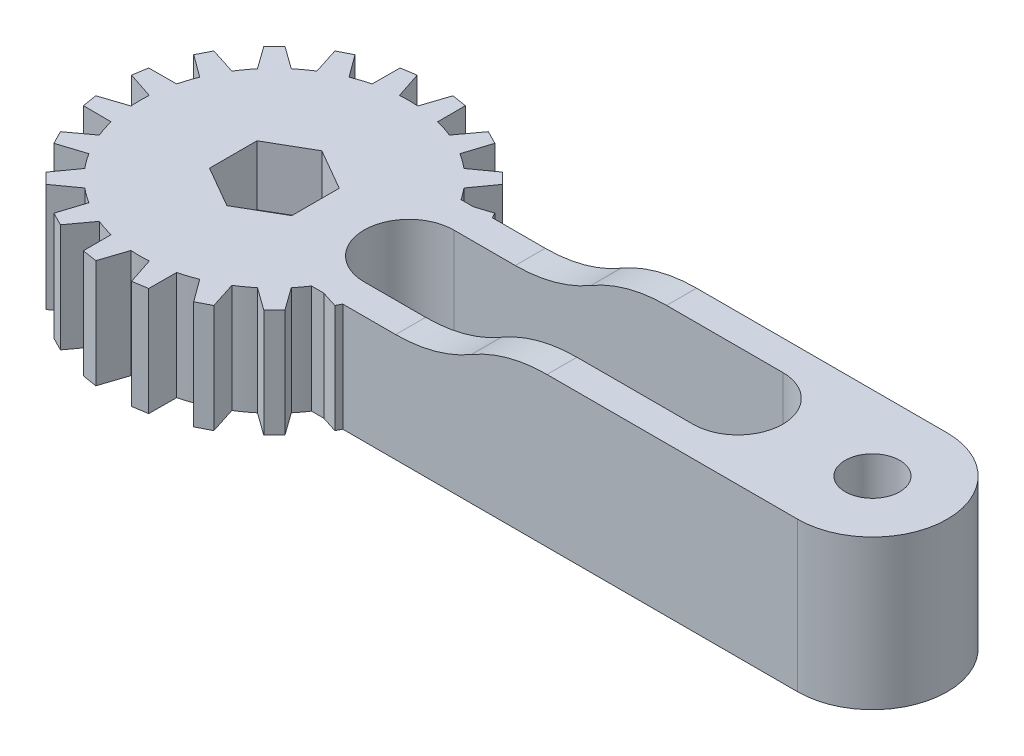
SolidWorks part; units mm, degrees
material "ABS"
ref_plane "Ebene vorne" through (0, 0, 0) normal (0, 0, 1) x (1, 0, 0)
ref_plane "Ebene oben" through (0, 0, 0) normal (0, 1, 0) x (1, 0, 0)
ref_plane "Ebene rechts" through (0, 0, 0) normal (1, 0, 0) x (0, 0, -1)
sketch "Skizze1" plane through (0, 0, 0) normal (0, 1, 0) x (1, 0, 0)
  line L0 (0, 0) -> (40, 0) construction
  line L1 (0, 5) -> (40, 5)
  line L2 (0, -5) -> (40, -5)
  arc A0 (0, 5) -> (0, -5) centre (0, 0) ccw
  arc A1 (40, -5) -> (40, 5) centre (40, 0) ccw
  circle A2 centre (40, 0) radius 1.825
  circle A3 centre (0, 0) radius 1.825
  point P3 (20, 0)
  dimension "D3" = 3.65
  dimension "D4" = 3.65
  dimension "D1" = 40
  dimension "D2" = 5
extrude "Aufsatz-Linear austragen1" add sketch "Skizze1" against normal blind 10
sketch "Skizze5" plane through (0, 0, 0) normal (0, 1, 0) x (1, 0, 0)
  line L0 (0, -5) -> (20, -5)
  line L1 (0, -5) -> (40, -5) construction
  line L2 (20, -5) -> (20, 5)
  line L3 (40, 5) -> (0, 5) construction
  line L4 (20, 5) -> (0, 5)
  arc A0 (0, 5) -> (0, -5) centre (0, 0) ccw
  arc A1 (0, 5) -> (0, -5) centre (0, 0) ccw construction
extrude "Schnitt-Linear austragen1" cut sketch "Skizze5" against normal blind 2.75
fillet "Verrundung1" radius 10 1 edges at (20, -2.75, 0)
fillet "Verrundung2" radius 10 1 edges at (20, 0, 0)
sketch "Skizze2" plane through (0, -2.75, 0) normal (0, 1, 0) x (1, 0, 0)
  circle A0 centre (0, 0) radius 5
  circle A1 centre (0, 0) radius 9
  arc A3 (0, 5) -> (0, -5) centre (0, 0) ccw construction
  dimension "D1" = 18
extrude "Aufsatz-Linear austragen2" add sketch "Skizze2" against normal up to surface (7.25 mm away) up to face at (0, -10, 1.825)
sketch "Skizze3" plane through (0, -2.75, 0) normal (0, 1, 0) x (1, 0, 0)
  line L0 (-12.8224, 0) -> (0, 0) construction
  line L1 (0, 0) -> (-12.8224, 2.0309) construction
  line L2 (-8.9792, 0.6122) -> (-10.7453, 1.1956)
  line L3 (-10.7453, 1.1956) -> (-10.5888, 2.1833)
  line L4 (-8.7289, 2.1925) -> (-10.5888, 2.1833)
  circle A0 centre (0, 0) radius 9 construction
  arc A1 (-8.9792, 0.6122) -> (-8.7289, 2.1925) centre (0, 0) cw
  point P5 (-8.8892, 1.4079)
  point P12 (-10.667, 1.6895)
  dimension "D1" = 9
  dimension "D2" = 0.5
  dimension "D3" = 0.8
  dimension "D4" = 1.8
extrude "Aufsatz-Linear austragen3" add sketch "Skizze3" against normal up to surface (7.25 mm away) up to face at (20.8708, -10, 0)
pattern_circular "Kreismuster1" count 20 over 360 about axis through (0, -2.75, 0) along (0, 1, 0) of "Aufsatz-Linear austragen3"
sketch "Skizze6" plane through (0, 0, 0) normal (0, 1, 0) x (1, 0, 0)
  line L1 (40, 3.1754) -> (37.25, 1.5877)
  line L2 (37.25, 1.5877) -> (37.25, -1.5877)
  line L3 (37.25, -1.5877) -> (40, -3.1754)
  line L4 (40, -3.1754) -> (42.75, -1.5877)
  line L5 (42.75, -1.5877) -> (42.75, 1.5877)
  line L6 (42.75, 1.5877) -> (40, 3.1754)
  circle A0 centre (40, 0) radius 2.75 construction
  dimension "D1" = 5.5
extrude "Schnitt-Linear austragen2" [suppressed] cut sketch "Skizze6" against normal blind 5
sketch "Skizze8" plane through (0, -2.75, 0) normal (0, 1, 0) x (1, 0, 0)
  line L1 (0, 3.1754) -> (-2.75, 1.5877)
  line L2 (-2.75, 1.5877) -> (-2.75, -1.5877)
  line L3 (-2.75, -1.5877) -> (0, -3.1754)
  line L4 (0, -3.1754) -> (2.75, -1.5877)
  line L5 (2.75, -1.5877) -> (2.75, 1.5877)
  line L6 (2.75, 1.5877) -> (0, 3.1754)
  circle A0 centre (0, 0) radius 2.75 construction
  dimension "D1" = 5.5
extrude "Schnitt-Linear austragen3" cut sketch "Skizze8" against normal blind 4
sketch "Skizze10" plane through (0, -10, 0) normal (0, -1, 0) x (1, 0, 0)
  line L0 (9, 0) -> (31, 0) construction
  line L1 (9, 3) -> (31, 3)
  line L2 (9, -3) -> (31, -3)
  arc A0 (9, 3) -> (9, -3) centre (9, 0) ccw
  arc A1 (31, -3) -> (31, 3) centre (31, 0) ccw
  point P3 (20, 0)
  dimension "D1" = 6
  dimension "D2" = 22
  dimension "D3" = 20
extrude "Schnitt-Linear austragen4" cut sketch "Skizze10" against normal through all
